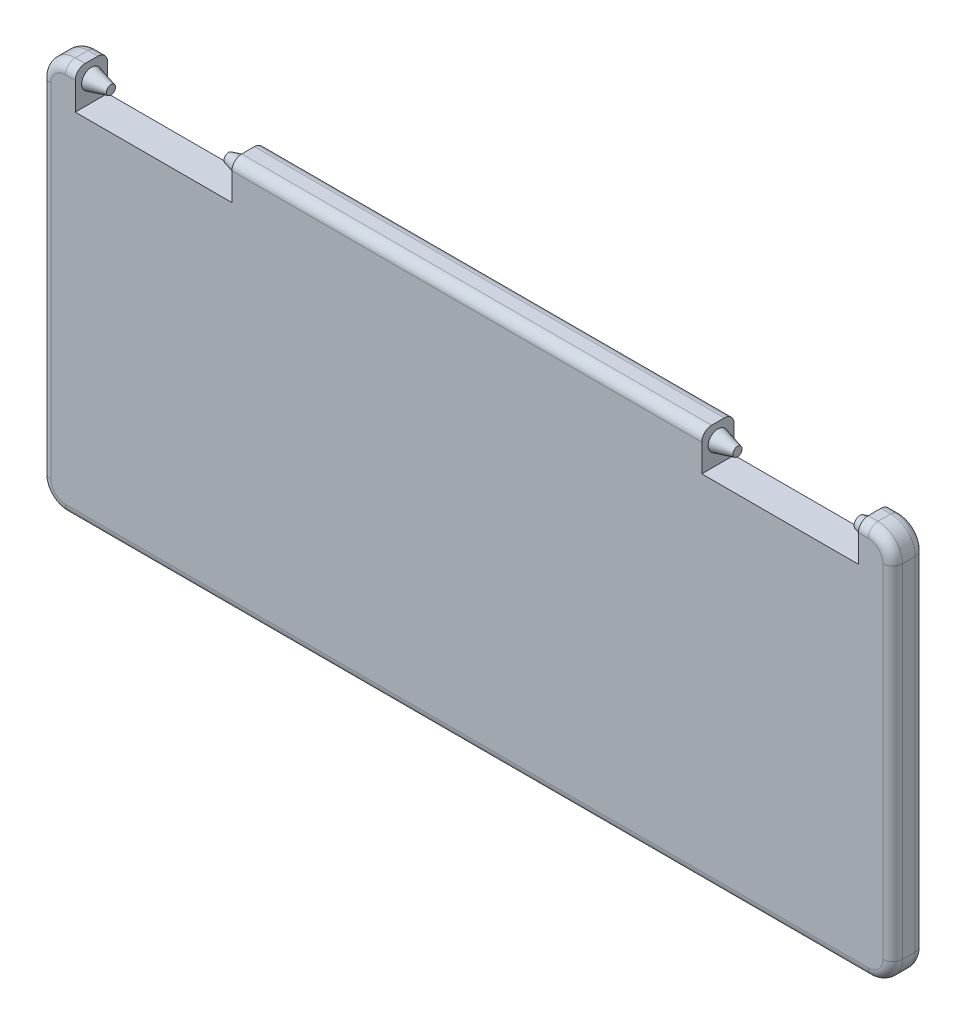
SolidWorks part; units mm, degrees
ref_plane "Front Plane" through (0, 0, 0) normal (0, 0, 1) x (1, 0, 0)
ref_plane "Top Plane" through (0, 0, 0) normal (0, 1, 0) x (1, 0, 0)
ref_plane "Right Plane" through (0, 0, 0) normal (1, 0, 0) x (0, 0, -1)
sketch "Sketch1" plane through (0, 0, 0) normal (0, 0, 1) x (1, 0, 0)
  line L1 (0, 80) -> (174, 80)
  line L2 (0, 80) -> (0, 0)
  line L3 (0, 0) -> (174, 0)
  line L4 (174, 80) -> (174, 0)
  dimension "D1" = 174
  dimension "D2" = 80
extrude "Boss-Extrude1" add sketch "Sketch1" along normal blind 6.6
fillet "Fillet1" radius 5 4 edges at (174, 0, 3.3) (0, 0, 3.3) (174, 80, 3.3) (0, 80, 3.3)
sketch "Sketch5" plane through (0, 0, 6.6) normal (0, 0, 1) x (1, 0, 0)
  line L1 (7, 80) -> (39, 80)
  line L2 (7, 80) -> (7, 72.4)
  line L3 (7, 72.4) -> (39, 72.4)
  line L4 (39, 80) -> (39, 72.4)
  line L6 (174, 5) -> (174, 75) construction
  line L15 (135, 80) -> (167, 80)
  line L16 (135, 80) -> (135, 72.4)
  line L17 (135, 72.4) -> (167, 72.4)
  line L18 (167, 80) -> (167, 72.4)
  line L23 (169, 80) -> (5, 80) construction
  line L24 (0, 75) -> (0, 5) construction
  dimension "D1" = 32
  dimension "D2" = 0
  dimension "D3" = 7.6
  dimension "D4" = 7
  dimension "D5" = 7
extrude "Cut-Extrude1" cut sketch "Sketch5" against normal up to surface (6.6 mm away) up to face at (87, 40, 0)
sketch "Sketch6" plane through (167, 0, 0) normal (-1, 0, 0) x (0, 0, 1)
  line L1 (0, 72.4) -> (0, 80) construction
  line L2 (0, 80) -> (6.6, 80) construction
  circle A0 centre (3.3, 76.7) radius 2
  dimension "D1" = 4
  dimension "D3" = 3.3
  dimension "D2" = 3.3
sketch "Sketch9" plane through (39, 0, 0) normal (-1, 0, 0) x (0, 0, 1)
  line L0 (0, 80) -> (6.6, 80) construction
  line L1 (0, 72.4) -> (0, 80) construction
  circle A0 centre (3.3, 76.7) radius 2
  dimension "D1" = 3.3
  dimension "D2" = 3.3
  dimension "D3" = 4
sketch "Sketch10" plane through (7, 0, 0) normal (1, 0, 0) x (0, 0, -1)
  line L0 (0, 80) -> (-6.6, 80) construction
  line L3 (-6.6, 80) -> (-6.6, 72.4) construction
  circle A0 centre (-3.3, 76.7) radius 2
  dimension "D1" = 4
  dimension "D3" = 3.3
  dimension "D2" = 3.3
sketch "Sketch13" plane through (135, 0, 0) normal (1, 0, 0) x (0, 0, -1)
  line L0 (0, 80) -> (-6.6, 80) construction
  line L3 (-6.6, 80) -> (-6.6, 72.4) construction
  circle A0 centre (-3.3, 76.7) radius 2
  dimension "D1" = 4
  dimension "D3" = 3.3
  dimension "D2" = 3.3
extrude "Boss-Extrude2" add sketch "Sketch13" along normal blind 4 draft 15 contours A0
extrude "Boss-Extrude5" add sketch "Sketch10" along normal blind 4 draft 15 contours A0
extrude "Boss-Extrude6" add sketch "Sketch9" along normal blind 4 draft 15 contours A0
extrude "Boss-Extrude9" add sketch "Sketch6" along normal blind 3 draft 15 contours A0
fillet "Zaoblit4" radius 2 20 edges at (168, 80, 6.6) (87, 80, 6.6) (6, 80, 6.6) (6, 80, 0) (168, 80, 0) (87, 80, 0) (172.5355, 78.5355, 6.6) (174, 40, 6.6) (172.5355, 1.4645, 6.6) (87, 0, 6.6) (1.4645, 1.4645, 6.6) (0, 40, 6.6) (1.4645, 78.5355, 6.6) (1.4645, 78.5355, 0) (0, 40, 0) (1.4645, 1.4645, 0) (87, 0, 0) (172.5355, 1.4645, 0) (174, 40, 0) (172.5355, 78.5355, 0)
